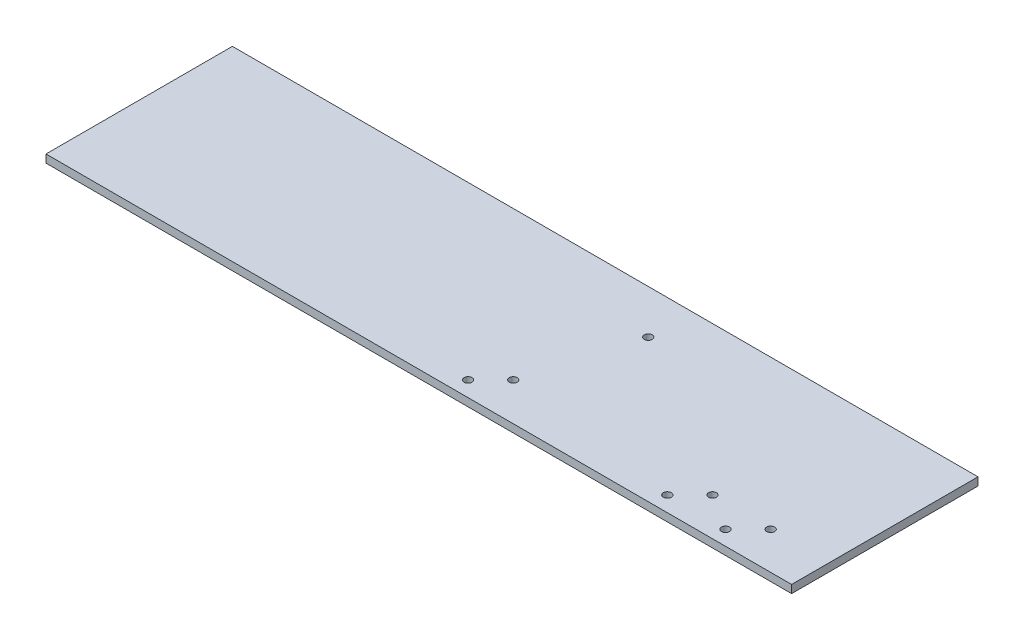
SolidWorks part; units mm, degrees
ref_plane "Front Plane" through (0, 0, 0) normal (0, 0, 1) x (1, 0, 0)
ref_plane "Top Plane" through (0, 0, 0) normal (0, 1, 0) x (1, 0, 0)
ref_plane "Right Plane" through (0, 0, 0) normal (1, 0, 0) x (0, 0, -1)
sketch "Sketch1" plane through (0, 0, 0) normal (0, 1, 0) x (1, 0, 0)
  line L1 (-140, -35) -> (140, -35)
  line L2 (-140, -35) -> (-140, 35)
  line L3 (-140, 35) -> (140, 35)
  line L4 (140, -35) -> (140, 35)
  line L5 (-140, -35) -> (140, 35) construction
  line L6 (-140, 35) -> (140, -35) construction
  circle A1 centre (87.5712, -29.2426) radius 1.5
  circle A2 centre (96.0565, -20.7574) radius 1.5
  circle A4 centre (109.6515, -29.4783) radius 1.5
  circle A5 centre (118.1368, -20.993) radius 1.5
  circle A6 centre (133.0434, 18.5) radius 1.5 construction
  circle A7 centre (40.6434, -29.2) radius 1.5 construction
  circle A8 centre (32.6434, -22.1) radius 1.5 construction
  circle A9 centre (32.6434, 18.5) radius 1.5
  circle A10 centre (12.7294, -29.2426) radius 1.5
  circle A11 centre (21.2147, -20.7574) radius 1.5
  point P0 (0, 0)
  dimension "D1" = 280
  dimension "D2" = 70
extrude "Boss-Extrude1" add sketch "Sketch1" along normal blind 3
